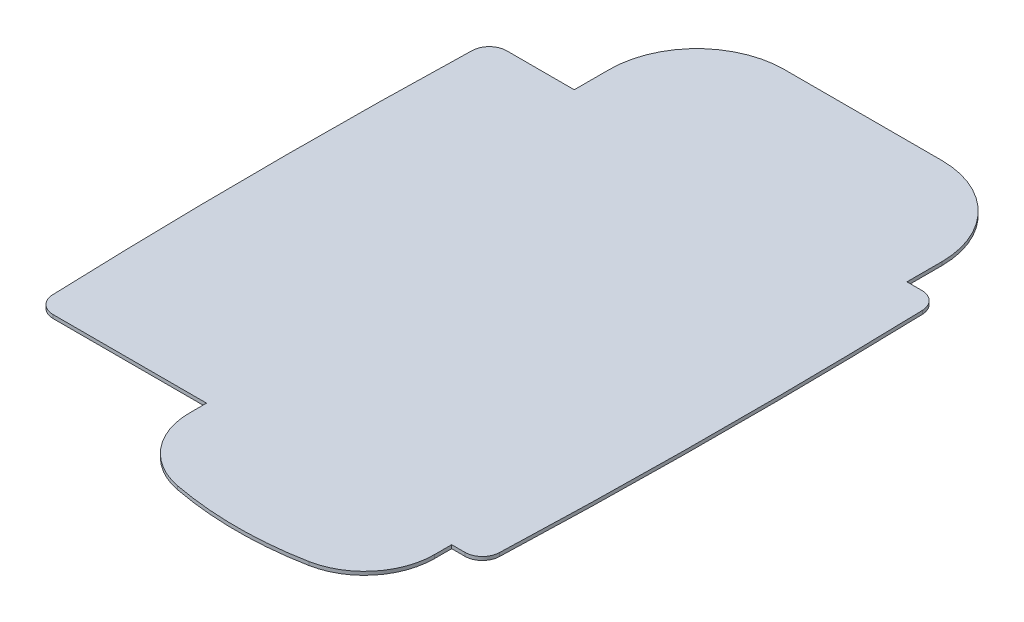
SolidWorks part; units mm, degrees
ref_plane "正面" through (0, 0, 0) normal (0, 0, 1) x (1, 0, 0)
ref_plane "平面" through (0, 0, 0) normal (0, 1, 0) x (1, 0, 0)
ref_plane "右側面" through (0, 0, 0) normal (1, 0, 0) x (0, 0, -1)
sketch "ｽｹｯﾁ1" plane through (0, 0, 0) normal (0, 1, 0) x (1, 0, 0)
  line L1 (-65, 92.5) -> (65, 92.5)
  line L2 (-65, 92.5) -> (-65, -92.5) construction
  line L3 (-65, -92.5) -> (65, -92.5)
  line L4 (65, 92.5) -> (65, -92.5) construction
  ellipse E0 centre (0, 0) end of major axis (0, -350) minor radius 65
  point P11 (-65, 0)
  dimension "D1" = 130
  dimension "D2" = 700
  dimension "D3" = 185
extrude "ﾎﾞｽ - 押し出し1" add sketch "ｽｹｯﾁ1" along normal mid plane 1 contours L3 E0 L1 region at (0, 0, 0)
sketch "ｽｹｯﾁ3" plane through (0, 0.5, 0) normal (0, 1, 0) x (1, 0, 0)
  line L0 (-62.6889, 92.5) -> (62.6889, 92.5) construction
  line L1 (-65, 92.5) -> (-40, 92.5)
  line L2 (-65, 92.5) -> (-65, 57.5)
  line L3 (-65, 57.5) -> (-40, 57.5)
  line L4 (-40, 92.5) -> (-40, 57.5)
  ellipse E0 centre (0, 0) end of major axis (0, -350) minor radius 65 (-62.6889, 92.5) -> (-62.6889, -92.5) ccw construction
  dimension "D1" = 35
  dimension "D2" = 25
extrude "ｶｯﾄ - 押し出し1" cut sketch "ｽｹｯﾁ3" against normal through all
sketch "ｽｹｯﾁ4" plane through (0, 0.5, 0) normal (0, 1, 0) x (1, 0, 0)
  line L0 (-40, 92.5) -> (62.6889, 92.5) construction
  line L1 (55, 92.5) -> (65, 92.5)
  line L2 (55, 92.5) -> (55, 57.5)
  line L3 (55, 57.5) -> (65, 57.5)
  line L4 (65, 92.5) -> (65, 57.5)
  line L5 (-64.1168, 57.5) -> (-40, 57.5) construction
  ellipse E0 centre (0, 0) end of major axis (0, -350) minor radius 65 (62.6889, -92.5) -> (62.6889, 92.5) ccw construction
  dimension "D1" = 10
extrude "ｶｯﾄ - 押し出し2" cut sketch "ｽｹｯﾁ4" against normal through all
sketch "ｽｹｯﾁ5" plane through (0, 0.5, 0) normal (0, 1, 0) x (1, 0, 0)
  line L0 (-62.6889, -92.5) -> (62.6889, -92.5) construction
  line L1 (-65, -72.5) -> (-15, -72.5)
  line L2 (-65, -72.5) -> (-65, -92.5)
  line L3 (-65, -92.5) -> (-15, -92.5)
  line L4 (-15, -72.5) -> (-15, -92.5)
  ellipse E0 centre (0, 0) end of major axis (0, -350) minor radius 65 (-64.1168, 57.5) -> (-62.6889, -92.5) ccw construction
  dimension "D1" = 20
  dimension "D2" = 50
extrude "ｶｯﾄ - 押し出し3" cut sketch "ｽｹｯﾁ5" against normal through all
sketch "ｽｹｯﾁ6" plane through (0, 0.5, 0) normal (0, 1, 0) x (1, 0, 0)
  line L0 (-15, -92.5) -> (62.6889, -92.5) construction
  line L1 (55, -72.5) -> (65, -72.5)
  line L2 (55, -72.5) -> (55, -92.5)
  line L3 (55, -92.5) -> (65, -92.5)
  line L4 (65, -72.5) -> (65, -92.5)
  line L7 (-15, -72.5) -> (-63.5902, -72.5) construction
  line L8 (55, 92.5) -> (55, 57.5) construction
  ellipse E0 centre (0, 0) end of major axis (0, -350) minor radius 65 (62.6889, -92.5) -> (64.1168, 57.5) ccw construction
extrude "ｶｯﾄ - 押し出し4" cut sketch "ｽｹｯﾁ6" against normal through all
sketch "ｽｹｯﾁ7" plane through (0, 0, 0) normal (0, 1, 0) x (1, 0, 0)
  line L0 (-15, -92.5) -> (55, -92.5) construction
  line L1 (-15, -92.5) -> (55, -92.5)
  arc A0 (-15, -92.5) -> (55, -92.5) centre (20, 1.175) ccw
  dimension "D1" = 100
extrude "ﾎﾞｽ - 押し出し2" add sketch "ｽｹｯﾁ7" along normal mid plane 1
sketch "ｽｹｯﾁ8" plane through (0, 0.5, 0) normal (0, 1, 0) x (1, 0, 0)
  line L0 (-40, 92.5) -> (55, 92.5) construction
  line L1 (-40, 57.5) -> (-40, 92.5) construction
  line L2 (55, 92.5) -> (55, 57.5) construction
  line L3 (55, 92.5) -> (55, 57.5)
  line L4 (-40, 92.5) -> (55, 92.5)
  line L5 (-40, 57.5) -> (-40, 92.5)
  circle A0 centre (-15, 67.5) radius 25
  circle A1 centre (30, 67.5) radius 25
  line M6 (55, 92.5) -> (-40, 92.5)
  line M7 (-40, 92.5) -> (-40, 57.5)
  dimension "D1" = 45
extrude "ｶｯﾄ - 押し出し5" cut sketch "ｽｹｯﾁ8" against normal through all contours A0 L4 M7 | A1 L3 M6 region at (49.4158, 0.5, -86.9158) region at (-34.4158, 0.5, -86.9158)
sketch "ｽｹｯﾁ9" plane through (0, 0, 0) normal (0, 1, 0) x (1, 0, 0)
  line L0 (-64.1168, 57.5) -> (-40, 57.5) construction
  line L1 (-65, 57.5) -> (-20, 57.5)
  line L2 (-65, 57.5) -> (-65, 5.5)
  line L3 (-65, 5.5) -> (-20, 5.5)
  line L4 (-20, 57.5) -> (-20, 5.5)
  arc A0 (-15, 92.5) -> (-40, 67.5) centre (-15, 67.5) ccw construction
  arc A1 (-15, 92.5) -> (-40, 67.5) centre (-15, 67.5) ccw
  circle A2 centre (-15, 67.5) radius 20
  ellipse E0 centre (0, 0) end of major axis (0, -350) minor radius 65 (-64.1168, 57.5) -> (-63.5902, -72.5) ccw construction
  dimension "D1" = 40
  dimension "D2" = 52
  dimension "D3" = 45
fillet "ﾌｨﾚｯﾄ1" radius 5 4 edges at (-64.1168, 0, -57.5) (-63.5902, 0, 72.5) (63.5902, 0, 72.5) (64.1168, 0, -57.5)
fillet "ﾌｨﾚｯﾄ2" radius 20 2 edges at (-15, 0, 92.5) (55, 0, 92.5)
